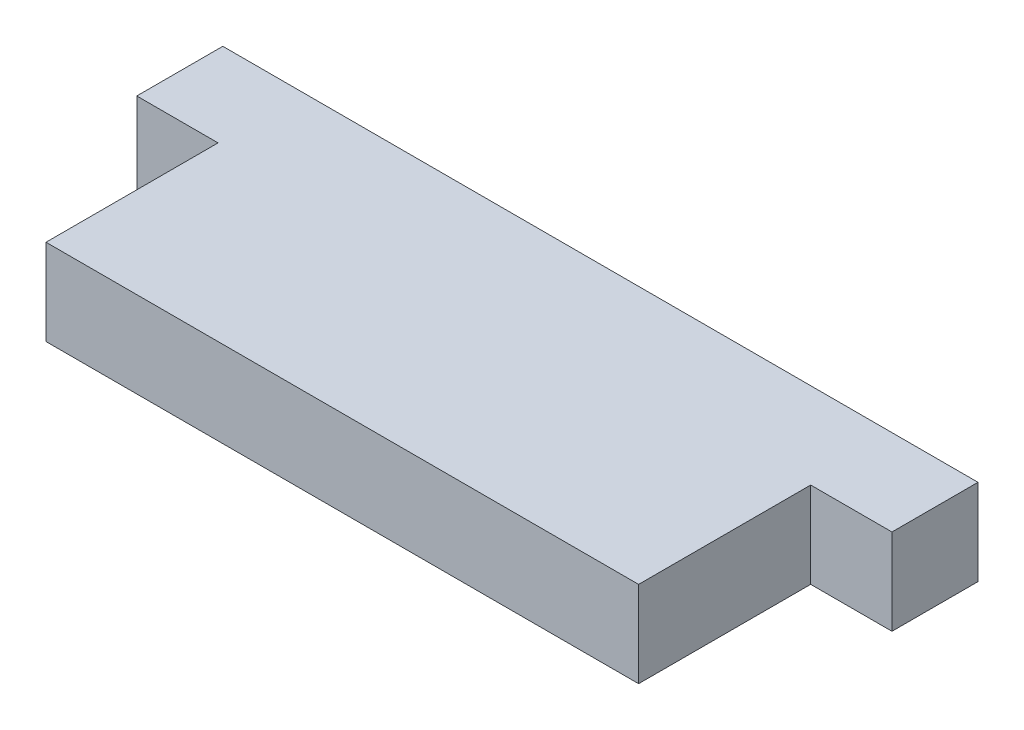
SolidWorks part; units mm, degrees
material "Beech"
ref_plane "Front Plane" through (0, 0, 0) normal (0, 0, 1) x (1, 0, 0)
ref_plane "Top Plane" through (0, 0, 0) normal (0, 1, 0) x (1, 0, 0)
ref_plane "Right Plane" through (0, 0, 0) normal (1, 0, 0) x (0, 0, -1)
sketch "Sketch1" plane through (0, 0, 0) normal (0, 1, 0) x (1, 0, 0)
  line L0 (0, 0) -> (0, 12.7)
  line L1 (0, 0) -> (43.74, 0)
  line L3 (43.74, 0) -> (43.74, 12.7)
  line L4 (-6, 19.05) -> (49.74, 19.05)
  line L5 (-6, 19.05) -> (-6, 12.7)
  line L6 (49.74, 19.05) -> (49.74, 12.7)
  line L7 (-6, 12.7) -> (0, 12.7)
  line L8 (43.74, 12.7) -> (49.74, 12.7)
  dimension "D1" = 12.7
  dimension "D2" = 43.74
  dimension "D3" = 6.35
  dimension "D4" = 6
  dimension "D5" = 6
extrude "Boss-Extrude1" add sketch "Sketch1" along normal blind 6.35
equation "\"MotorMountLegLength\"=.25in"
equation "\"GearOffset\"=.264907in"
equation "\"D4@Sketch1\"=\"TriggerRackOffset\""
equation "\"D5@Sketch1\"=\"TriggerRackOffset\""
equation "\"D2@Sketch1\" = \"CageLeftBottomEdge\" + \"CageRightBottomEdge\""
equation "\"CageLeftBottomEdge\"=22.11mm"
equation "\"CageLeftTopEdge\"=22.11mm"
equation "\"CageRightBottomEdge\"=21.63mm"
equation "\"CageRightTopEdge\"=21.63mm"
equation "\"CageHeight\"=86.04mm"
equation "\"CageLength\"=73.76mm"
equation "\"CageTopScrewClearance\"=10mm"
equation "\"CageBottomScrewClearance\"=25mm"
equation "\"CageLeftTopDepth\"= 11.65mm"
equation "\"CageLeftBottomDepth\"=11.11mm"
equation "\"CageLeftTopHeight\"=8.56175mm"
equation "\"CageLeftBottomHeight\"=16mm"
equation "\"CageRightTopDepth\"= 11.05mm"
equation "\"CageRightBottomDepth\"=10.58mm"
equation "\"CageRightTopHeight\"=9.6mm"
equation "\"CageRightBottomHeight\"=15.49mm"
equation "\"CageLeftTopChannelDepth\"=2.41908mm"
equation "\"CageLeftBottomChannelDepth\"=2.588mm"
equation "\"CageLeftChannelHeight\"=11.7mm"
equation "\"CageRightTopChannelDepth\"=2.32mm"
equation "\"CageRightBottomChannelDepth\"=2.318mm"
equation "\"CageRightChannelHeight\"=10mm"
equation "\"CageChanRelHeight\"=23.99mm"
equation "\"CageChanRelDepth\"=5.492mm"
equation "\"CageChamberRadius\"=16.261mm"
equation "\"CageScrewDiameter\"=4.8mm"
equation "\"CageSetScrewDiameter\"=3.5mm"
equation "\"CageAxleRadius\"=6.639mm"
equation "\"CageAxleKeyHeight\"=1.619mm"
equation "\"CageAxleKeyWidth\"=2.662mm"
equation "\"CageHoseWindowWidth\"=16.29mm"
equation "\"CageHoseWindowHeight\"=26.5mm"
equation "\"CageHoseWindow-Edge\"=8.89mm"
equation "\"CageScrew-VerticalEdge\"=5.0mm"
equation "\"CageScrew-HorizontalEdge\"=7.5mm"
equation "\"CageScrew-HoseCornerScrewEdge\"=4.45mm"
equation "\"CageAxle-BottomEdge\"=56.05mm"
equation "\"CageAxle-FrontEdge\"=46.03mm"
equation "\"CageBackSetScrew-Axle\"=40mm"
equation "\"CageFrontSetScrew-Axle\"=22mm"
equation "\"CageVelocityWindow-BackEdge\"=34.8mm"
equation "\"CageVelocityWindow-BottomEdge\"=27.55mm"
equation "\"CageVelocityWindowHeight\"=22.29mm"
equation "\"CageVelocityWindowWidth\"=12.61mm"
equation "\"TriggerSlot-BottomEdge\"=6.35mm"
equation "\"TriggerSlot-FrontEdge\"=15mm"
equation "\"TriggerSlotSize\"=6.7mm"
equation "\"TriggerRackOffset\"=6mm"
equation "\"TriggerSlotSizeInt\"=.25in"
equation "\"TriggerSlotSpacing\"=.25in"
equation "\"TriggerMiniSlotWidth\"=3.5mm"
equation "\"TriggerRackWidth\"=6.5mm"
equation "\"pandiscradius\"=14in"
equation "\"towermaterialwidth\"=.25in"
equation "\"towerslotlength\"=.5in"
equation "\"towermarkerspace\"=5in"
equation "\"towerslothorizoffset\"=1in"
equation "\"towerslothorizspacing\"=2in"
equation "\"towerslotvertoffset\"=3in"
equation "\"towerslotvertspacing\"=1in"
equation "\"towerheight\"=12in"
equation "\"towerupslot\"=1in"
equation "\"toweraxle\"=.5in"
equation "\"stepperouterrad\"=10mm"
equation "\"stepperscrewsize\"=3.45mm"
equation "\"stepperscrewc2c\"=49.5mm"
equation "\"stepperdepthoffset\"=24mm"
equation "\"stepperhorizoffset\"=22.91mm"
equation "\"shaftslotOD\"=18.8mm"
equation "\"shaftslotID\"=13.28mm"
equation "\"shaftkeywidth\"=2.67mm"
equation "\"shaftkeydepth\"=1.8mm"
equation "\"shaftcollartotaldepth\"=12.5mm"
equation "\"shaftsquaredepth\"=6mm"
equation "\"shaftsetscrewsize\"=3.5mm"
equation "\"shaftkeytightdepth\"=1.85mm"
equation "\"shaftslottightID\"=12.78mm"
equation "\"shaftsetscrewoffset\"=9mm"
equation "\"cagecollartotaldepth\"=10mm"
equation "\"cagecollartotalwidth\"=35mm"
equation "\"cagecollarbasedepth\"=4mm"
equation "\"gearhubintdiam\"=30mm"
equation "\"gearhubintwid\"=15mm"
equation "\"towerspeedwidth\"=2in"
equation "\"towerspeedheight\"=8in"
equation "\"towerspeedgap\"=2in"
equation "\"stepperaxleflat\"=.037in"
equation "\"stepperaxlerad\"=0.11811024in"
equation "\"ajaxaxlesize\"=3.87mm"
equation "\"ajaxinnercut\"=2.3mm"
equation "\"ajaxwidth\"=6.1mm"
equation "\"ajaxdiametral\"=25.8854"
equation "\"ajaxcutoutdepth\"=2.3mm"
equation "\"ajax4020gap\"=29.5mm"
equation "\"ajax4010gap\"=24.5mm"
equation "\"ajax20hubbuffer\"=6.1mm"
equation "\"ajax20hubholeoffset\"=.19685in"
equation "\"ajax20hubholesize\"=.059055in"
equation "\"ajax20cutoutint\"=13.4mm"
equation "\"ajax40hubholesize\"=7.21mm"
equation "\"ajax40hubholeoffset\"=10mm"
equation "\"ajax40hubbuffer\"=8.9mm"
equation "\"ajax40cutoutint\"=32.6mm"
equation "\"bearingpandiscrad\"=6.8in"
equation "\"bearingpandiscang\"=48.75deg"
equation "\"bearingclearholedist\"=4.7345in"
equation "\"bearingclearholesize\"=.5in"
equation "\"bearingclearholeang\"=22.5deg"
equation "\"bearingmountholedist\"=4.25in"
equation "\"bearingwirehole\"=1.5in"
equation "\"no6diam\"=.146in"
equation "\"shortconangle\"=20deg"
equation "\"shortconlen\"=.875in"
equation "\"longconlen\"=1.25in"
equation "\"longconangle\"=15deg"
